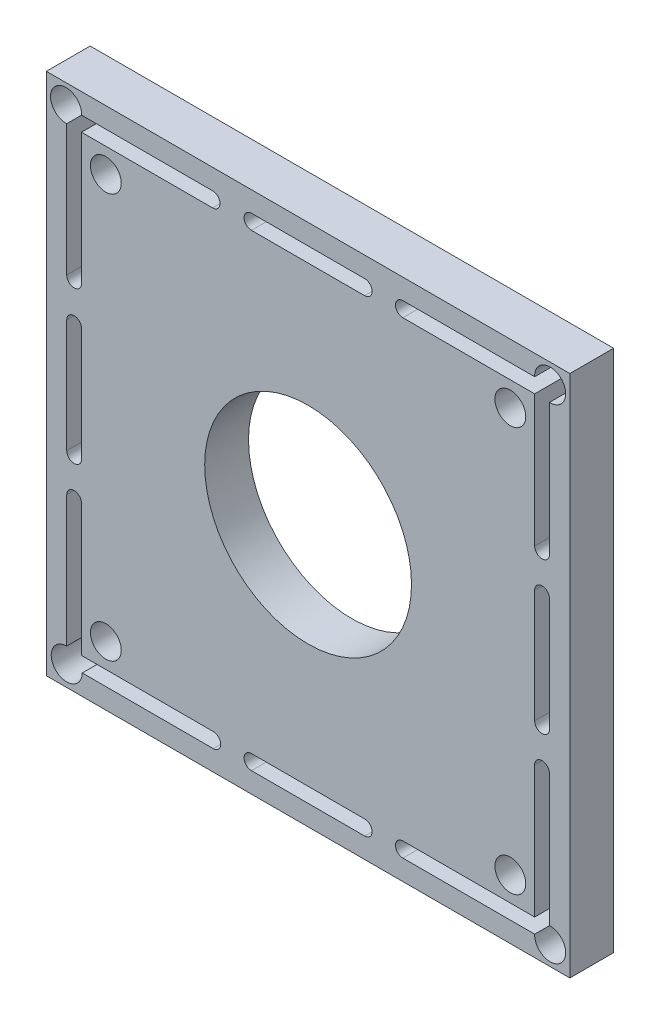
SolidWorks part; units mm, degrees
ref_plane "Front Plane" through (0, 0, 0) normal (0, 0, 1) x (1, 0, 0)
ref_plane "Top Plane" through (0, 0, 0) normal (0, 1, 0) x (1, 0, 0)
ref_plane "Right Plane" through (0, 0, 0) normal (1, 0, 0) x (0, 0, -1)
sketch "Sketch1" plane through (0, 0, 0) normal (0, 0, 1) x (1, 0, 0)
  line L1 (0, 37.9349) -> (37.9349, 37.9349)
  line L2 (0, 37.9349) -> (0, 0)
  line L3 (0, 0) -> (37.9349, 0)
  line L4 (37.9349, 37.9349) -> (37.9349, 0)
  dimension "D1" = 37.9349
extrude "Boss-Extrude1" add sketch "Sketch1" along normal blind 3.175
sketch "Sketch9" plane through (0, 0, 3.175) normal (0, 0, 1) x (1, 0, 0)
  line L0 (33.6232, 33.6232) -> (35.9219, 33.6232) construction
  line L1 (0, 0) -> (37.9349, 0) construction
  line L2 (2.5493, 18.9674) -> (1.4766, 18.9675) construction
  line L3 (33.6232, 35.922) -> (33.6232, 33.6232) construction
  line L4 (0, 37.9349) -> (0, 0) construction
  line L5 (35.3856, 12.1002) -> (36.4583, 12.1002) construction
  line L6 (4.3117, 35.9219) -> (4.3117, 33.6232) construction
  line L7 (2.013, 33.6232) -> (4.3117, 33.6232) construction
  line L8 (4.3117, 2.013) -> (4.3117, 4.3117) construction
  line L9 (2.0129, 4.3117) -> (4.3117, 4.3117) construction
  line L10 (35.9219, 4.3117) -> (33.6232, 4.3117) construction
  line L11 (33.6232, 2.013) -> (33.6232, 4.3117) construction
  line L12 (35.3856, 12.1002) -> (35.3856, 2.5493)
  line L13 (35.3856, 2.5493) -> (25.8347, 2.5493)
  line L14 (35.3856, 1.4766) -> (25.8347, 1.4766)
  line L15 (35.3856, 36.4583) -> (25.8347, 36.4583)
  line L16 (37.9349, 37.9349) -> (0, 37.9349) construction
  line L17 (12.0489, 36.4583) -> (2.5493, 36.4583)
  line L18 (12.0489, 36.4583) -> (12.0489, 35.3856) construction
  line L19 (12.0489, 35.3856) -> (2.5493, 35.3856)
  line L20 (35.922, 35.9219) -> (2.0129, 35.9219) construction
  line L21 (23.0695, 36.4583) -> (14.8653, 36.4583)
  line L22 (35.922, 35.9219) -> (35.922, 2.013) construction
  line L23 (35.922, 2.013) -> (2.013, 2.013) construction
  line L24 (2.0129, 35.9219) -> (2.013, 2.013) construction
  line L25 (18.9674, 37.9349) -> (18.9674, 0) construction
  line L26 (23.0695, 36.4583) -> (23.0695, 35.3856) construction
  line L27 (23.0695, 35.3856) -> (14.8653, 35.3856)
  line L28 (0, 0) -> (37.9349, 0) construction
  line L29 (25.8347, 2.5493) -> (25.8347, 1.4766) construction
  line L30 (14.8653, 36.4583) -> (14.8653, 35.3856) construction
  line L31 (35.3856, 2.5493) -> (36.4583, 2.5493) construction
  line L32 (35.922, 18.9674) -> (2.013, 18.9674) construction
  line L33 (2.5493, 36.4583) -> (2.5493, 35.3856) construction
  line L34 (2.5493, 35.3856) -> (1.4766, 35.3856) construction
  line L35 (2.5493, 12.1002) -> (1.4766, 12.1002) construction
  line L36 (36.4583, 12.1002) -> (36.4583, 2.5493)
  line L37 (35.3856, 35.3856) -> (25.8347, 35.3856)
  line L38 (2.5493, 35.3856) -> (2.5493, 25.886)
  line L39 (12.1002, 2.5493) -> (12.1002, 1.4766) construction
  line L42 (25.8347, 36.4583) -> (25.8347, 35.3856) construction
  line L43 (35.3856, 35.3856) -> (36.4583, 35.3856) construction
  line L44 (35.3856, 35.3856) -> (35.3856, 25.8347)
  line L45 (35.3856, 25.8347) -> (36.4583, 25.8347) construction
  line L46 (36.4583, 35.3856) -> (36.4583, 25.8347)
  line L47 (2.5493, 25.886) -> (1.4766, 25.886) construction
  line L48 (1.4766, 35.3856) -> (1.4766, 25.886)
  line L49 (2.5493, 23.0696) -> (1.4766, 23.0696) construction
  line L50 (2.5493, 23.0696) -> (2.5493, 14.8654)
  line L51 (2.5493, 14.8654) -> (1.4766, 14.8654) construction
  line L52 (1.4766, 23.0696) -> (1.4766, 14.8654)
  line L53 (36.4583, 18.9675) -> (35.3856, 18.9675) construction
  line L54 (36.4583, 23.0695) -> (35.3856, 23.0695) construction
  line L55 (36.4583, 23.0695) -> (36.4583, 14.8654)
  line L56 (36.4583, 14.8654) -> (35.3856, 14.8654) construction
  line L57 (35.3856, 23.0695) -> (35.3856, 14.8654)
  line L58 (18.9674, 36.4583) -> (18.9674, 35.3856) construction
  line L59 (18.9674, 2.5493) -> (18.9674, 1.4766) construction
  line L60 (23.0695, 2.5493) -> (14.8653, 2.5493)
  line L61 (23.0695, 2.5493) -> (23.0695, 1.4766) construction
  line L62 (23.0695, 1.4766) -> (14.8653, 1.4766)
  line L63 (14.8653, 2.5493) -> (14.8653, 1.4766) construction
  line L68 (2.5493, 12.1002) -> (2.5493, 2.5493)
  line L69 (1.4766, 12.1002) -> (1.4766, 2.6006)
  line L70 (2.5493, 2.5493) -> (12.1002, 2.5493)
  line L71 (2.6006, 1.4766) -> (12.1002, 1.4766)
  line L75 (12.1002, 2.013) -> (12.6365, 2.013) construction
  line L76 (2.013, 2.013) -> (2.013, 0) construction
  line L77 (0, 2.0129) -> (2.013, 2.013) construction
  circle A0 centre (33.6232, 33.6232) radius 1.1176
  circle A1 centre (4.3117, 33.6232) radius 1.1176
  circle A2 centre (4.3117, 4.3117) radius 1.1176
  circle A3 centre (33.6232, 4.3117) radius 1.1176
  arc A4 (25.8347, 1.4766) -> (25.8347, 2.5493) centre (25.8347, 2.013) cw
  arc A5 (36.4583, 2.5493) -> (35.3856, 1.4766) centre (36.5084, 1.4265) cw
  arc A6 (14.8653, 36.4583) -> (14.8653, 35.3856) centre (14.8653, 35.9219) ccw
  arc A7 (23.0695, 36.4583) -> (23.0695, 35.3856) centre (23.0695, 35.9219) cw
  arc A8 (1.4766, 2.6006) -> (2.6006, 1.4766) centre (1.4766, 1.4766) ccw
  arc A9 (36.4583, 12.1002) -> (35.3856, 12.1002) centre (35.9219, 12.1002) ccw
  arc A10 (12.0489, 35.3856) -> (12.0489, 36.4583) centre (12.0489, 35.9219) ccw
  arc A11 (1.4766, 35.3856) -> (2.5493, 36.4583) centre (1.4265, 36.5084) cw
  arc A12 (36.4583, 25.8347) -> (35.3856, 25.8347) centre (35.922, 25.8347) cw
  arc A13 (25.8347, 35.3856) -> (25.8347, 36.4583) centre (25.8347, 35.9219) cw
  arc A14 (36.4583, 35.3856) -> (35.3856, 36.4583) centre (36.5084, 36.5084) ccw
  arc A15 (2.5493, 25.886) -> (1.4766, 25.886) centre (2.013, 25.886) cw
  arc A16 (2.5493, 23.0696) -> (1.4766, 23.0696) centre (2.0129, 23.0695) ccw
  arc A17 (1.4766, 14.8654) -> (2.5493, 14.8654) centre (2.0129, 14.8654) ccw
  arc A18 (1.4766, 12.1002) -> (2.5493, 12.1002) centre (2.0129, 12.1002) cw
  arc A19 (12.1002, 2.5493) -> (12.1002, 1.4766) centre (12.1002, 2.013) cw
  arc A20 (36.4583, 23.0695) -> (35.3856, 23.0695) centre (35.922, 23.0695) ccw
  arc A21 (36.4583, 14.8654) -> (35.3856, 14.8654) centre (35.922, 14.8653) cw
  arc A22 (14.8653, 2.5493) -> (14.8653, 1.4766) centre (14.8654, 2.0129) ccw
  arc A23 (23.0695, 1.4766) -> (23.0695, 2.5493) centre (23.0695, 2.0129) ccw
  point P47 (18.9674, 18.9674)
  point P66 (2.0129, 18.9674)
  point P89 (35.922, 18.9674)
  dimension "D1" = 9.4996
  dimension "D3" = 2.013
  dimension "D4" = 2.2352
  dimension "D6" = 8.2042
  dimension "D5" = 1.1239
  dimension "D7" = 1.0727
  dimension "D2" = 2.2987
extrude "Cut-Extrude2" cut sketch "Sketch9" against normal up to surface (3.175 mm away) up to face at (18.9674, 18.9675, 0)
sketch "Sketch10" plane through (0, 0, 0) normal (0, 0, -1) x (-1, 0, 0)
  line L0 (-18.9674, 37.9349) -> (-18.9674, 0) construction
  line L1 (-37.9349, 37.9349) -> (0, 37.9349) construction
  line L2 (0, 0) -> (-37.9349, 0) construction
  circle A0 centre (-18.9674, 18.9674) radius 7.493
  dimension "D1" = 14.986
extrude "Cut-Extrude3" cut sketch "Sketch10" against normal up to surface (3.175 mm away) up to face at (18.9674, 2.0129, 3.175)
